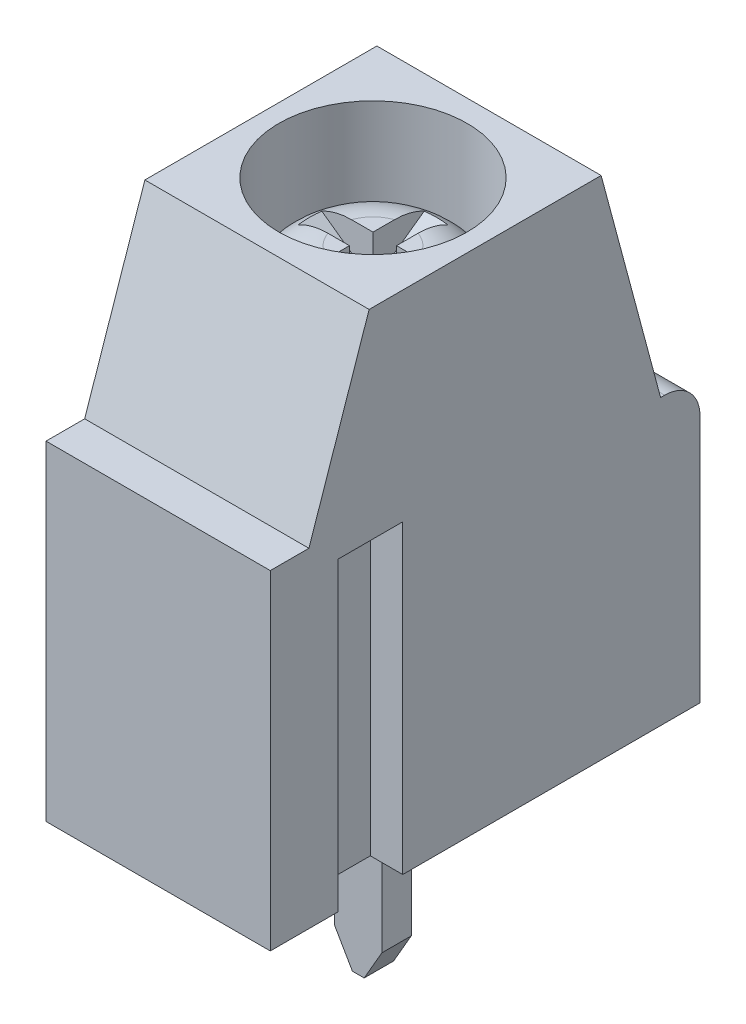
SolidWorks part; units mm, degrees
ref_plane "Plano frontal" through (0, 0, 0) normal (0, 0, 1) x (1, 0, 0)
ref_plane "Plano superior" through (0, 0, 0) normal (0, 1, 0) x (1, 0, 0)
ref_plane "Plano direito" through (0, 0, 0) normal (1, 0, 0) x (0, 0, -1)
sketch "Sketch1" plane through (0, 0, 0) normal (1, 0, 0) x (0, 0, -1)
  line L0 (7.3, 0) -> (7.3, 8.6) construction
  line L1 (0, 0) -> (0, 8.6) construction
  line L2 (7.3, 8.6) -> (0, 8.6) construction
  line L3 (5.6209, 8.6) -> (6.6312, 4.8275)
  line L4 (5.6209, 8.6) -> (1.6791, 8.6)
  line L5 (7.3, 0) -> (0, 0)
  line L6 (6.6312, 4.8275) -> (6.7, 4.8275)
  line L7 (7.3, 4.2275) -> (7.3, 0)
  line L8 (1.6791, 8.6) -> (0.6561, 5.5972)
  line L9 (0.6561, 5.5972) -> (0, 5.5972)
  line L10 (0, 5.5972) -> (0, 0)
  arc A0 (6.7, 4.8275) -> (7.3, 4.2275) centre (6.7, 4.2275) cw
  point P10 (3.65, 8.6)
  point P14 (5.6209, 8.6)
  dimension "D1" = 0.6
  dimension "D2" = 8.6
  dimension "D3" = 7.3
extrude "Boss-Extrude1" add sketch "Sketch1" along normal blind 3.81
ref_plane "Плоскость6" through (0.4, 0, 0) normal (-1, 0, 0) x (0, 0, 1)
sketch "Эскиз2" plane through (0.4, 0, 0) normal (-1, 0, 0) x (0, 0, 1)
  line L0 (-7.3, 4.0736) -> (-6.0323, 3.4261)
  line L1 (-6.0323, 3.4261) -> (-2.9311, 3.4261)
  line L2 (-2.9311, 3.4261) -> (-2.9311, 0.8037)
  line L3 (-2.9311, 0.8037) -> (-6.2624, 0.8037)
  line L4 (-6.2624, 0.8037) -> (-7.3, 0.3636)
  line L5 (-7.3, 4.0736) -> (-7.3, 0.3636)
  line L6 (-7.3, 0) -> (-7.3, 4.2275) construction
  dimension "D1" = 0
extrude "Вырез-Вытянуть1" cut sketch "Эскиз2" against normal blind 3.01
sketch "Эскиз4" plane through (0, 8.6, 0) normal (0, 1, 0) x (1, 0, 0)
  line L0 (1.905, 1.6791) -> (1.905, 5.6209) construction
  line L1 (3.81, 1.6791) -> (0, 1.6791) construction
  line L2 (3.81, 5.6209) -> (0, 5.6209) construction
  circle A0 centre (1.905, 3.65) radius 1.6
extrude "Вырез-Вытянуть2" cut sketch "Эскиз4" against normal blind 4 contours A0
ref_plane "Плоскость10" through (1.905, 0, 0) normal (-1, 0, 0) x (0, 0, 1)
sketch "Эскиз5" plane through (1.905, 0, 0) normal (-1, 0, 0) x (0, 0, 1)
  line L0 (-5.6209, 8.6) -> (-1.6791, 8.6) construction
  line L1 (-3.65, 7.6) -> (-4.25, 7.6)
  line L2 (-3.65, 7.6) -> (-3.65, 5.6944)
  line L3 (-3.65, 5.6944) -> (-5.25, 5.6944)
  line L4 (-5.25, 6.6) -> (-5.25, 5.6944)
  line L6 (0, 5.5972) -> (0, 0) construction
  arc A0 (-4.25, 7.6) -> (-5.25, 6.6) centre (-4.25, 6.6) ccw
  point P6 (-5.25, 7.6)
  dimension "D2" = 1
  dimension "D1" = 1.6
  dimension "D3" = 3.65
  dimension "D4" = 1.9056
  dimension "D5" = 1
revolve "Повернуть1" add sketch "Эскиз5" angle 360 about L2
sketch "Эскиз7" plane through (0, 0, 0) normal (-1, 0, 0) x (0, 0, 1)
  line L0 (0, 0) -> (-7.3, 0) construction
  line L1 (-2.2, 5.1397) -> (-1.2, 5.1397)
  line L2 (-2.2, 5.1397) -> (-2.2, 0)
  line L3 (-2.2, 0) -> (-1.2, 0)
  line L4 (-1.2, 5.1397) -> (-1.2, 0)
  line L6 (0, 5.5972) -> (0, 0) construction
  dimension "D1" = 1
  dimension "D2" = 1.2
extrude "Бобышка-Вытянуть1" add sketch "Эскиз7" along normal blind 0.5 contours L4 L3 L2 L1
sketch "Эскиз8" plane through (3.81, 0, 0) normal (1, 0, 0) x (0, 0, -1)
  line L0 (2.2, 5.1397) -> (2.2, 0) construction
  line L1 (1.15, 5.1897) -> (2.25, 5.1897)
  line L2 (1.15, 5.1897) -> (1.15, 0)
  line L3 (1.15, 0) -> (2.25, 0)
  line L4 (2.25, 5.1897) -> (2.25, 0)
  line L5 (1.2, 5.1397) -> (1.2, 0) construction
  line L6 (2.2, 5.1397) -> (1.2, 5.1397) construction
  dimension "D1" = 0.05
  dimension "D2" = 0.05
  dimension "D3" = 0.05
extrude "Вырез-Вытянуть4" cut sketch "Эскиз8" against normal blind 0.55
sketch "Эскиз10" plane through (0, 0, 0) normal (0, -1, 0) x (-1, 0, 0)
  line L0 (-1.905, -3.0915) -> (-1.905, 3.0915) construction
  line L1 (-2.305, 3.4) -> (-1.505, 3.4)
  line L2 (-2.305, 3.4) -> (-2.305, 3.9)
  line L3 (-2.305, 3.9) -> (-1.505, 3.9)
  line L4 (-1.505, 3.4) -> (-1.505, 3.9)
  line L5 (-2.305, 3.4) -> (-1.505, 3.9) construction
  line L6 (-2.305, 3.9) -> (-1.505, 3.4) construction
  point P0 (-1.905, 3.65)
  dimension "D1" = 0.8
  dimension "D2" = 0
  dimension "D3" = 0.5
extrude "Бобышка-Вытянуть2" add sketch "Эскиз10" along normal blind 3 contours L3 L4 L1 L2
chamfer "Фаска2" distance 0.3 angle 60 1 edges at (1.505, -3, -3.65) first distance on face at (1.905, -3, -3.65)
chamfer "Фаска3" distance 0.3 angle 60 1 edges at (2.305, -3, -3.65) first distance on face at (2.055, -3, -3.65)
sketch "Эскиз11" plane through (1.905, 0, 0) normal (-1, 0, 0) x (0, 0, 1)
  line L0 (-4.9098, 7.9962) -> (-3.65, 7.9962)
  line L1 (-3.65, 7.9962) -> (-3.65, 6.8516)
  line L3 (-4.9098, 7.6079) -> (-4.9098, 7.9962)
  line L4 (-5.6209, 8.6) -> (-1.6791, 8.6) construction
  line L5 (-3.65, 6.8516) -> (-3.85, 6.8516)
  line L6 (-4.9098, 7.6079) -> (-3.85, 6.8516)
  point P6 (-3.65, 8.6)
  dimension "D1" = 0
  dimension "D2" = 0.2
extrude "Вырез-Вытянуть5" cut sketch "Эскиз11" against normal blind 0.4 from offset 0.2 contours L0 L1 L5 L6 L3
ref_axis "Ось1" through (1.905, 6.6, -3.65) along (0, 1, 0)
pattern_circular "Круговой массив1" count 4 every 90 about axis through (1.905, 6.6, -3.65) along (0, 1, 0) of "Вырез-Вытянуть5"
